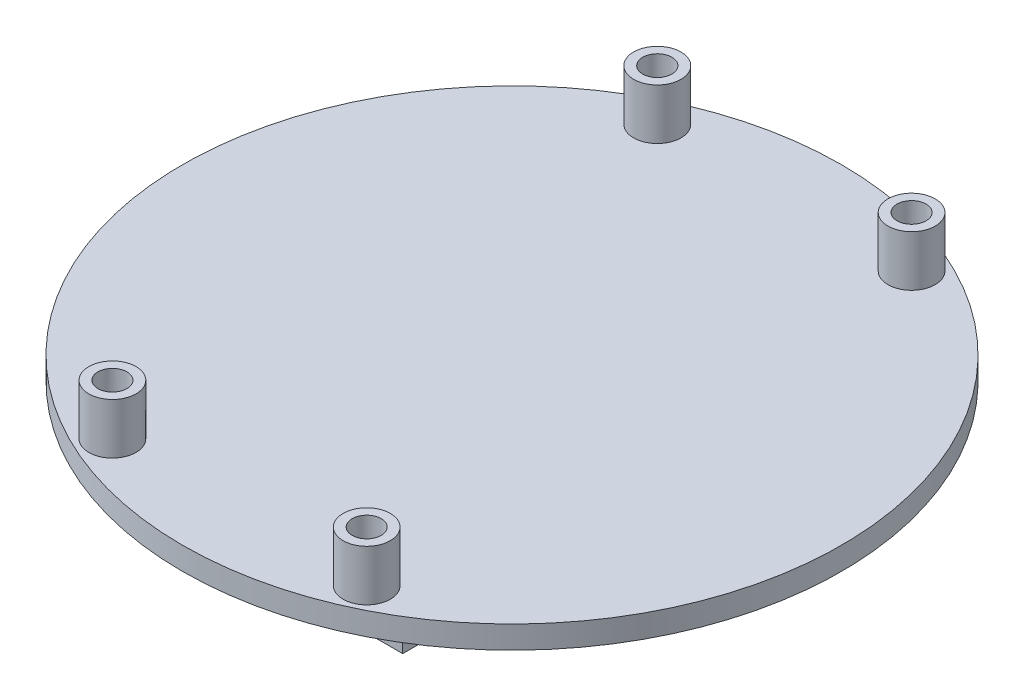
SolidWorks part; units mm, degrees
ref_plane "Alzado" through (0, 0, 0) normal (0, 0, 1) x (1, 0, 0)
ref_plane "Planta" through (0, 0, 0) normal (0, 1, 0) x (1, 0, 0)
ref_plane "Vista lateral" through (0, 0, 0) normal (1, 0, 0) x (0, 0, -1)
sketch "Croquis1" plane through (0, 0, 0) normal (0, 1, 0) x (1, 0, 0)
  circle A0 centre (0, 0) radius 36.29
  dimension "D1" = 72.58
extrude "Saliente-Extruir1" add sketch "Croquis1" along normal mid plane 2.5
sketch "Croquis2" plane through (0, -1.25, 0) normal (0, -1, 0) x (1, 0, 0)
  line L0 (-14.97, 27.005) -> (14.97, 27.005)
  line L1 (-13.97, -26.005) -> (13.97, -26.005)
  line L2 (-13.97, -26.005) -> (-13.97, 26.005)
  line L3 (-13.97, 26.005) -> (13.97, 26.005)
  line L4 (13.97, -26.005) -> (13.97, 26.005)
  line L5 (-13.97, -26.005) -> (13.97, 26.005) construction
  line L6 (-13.97, 26.005) -> (13.97, -26.005) construction
  line L7 (14.97, -27.005) -> (14.97, 27.005)
  line L8 (-14.97, -27.005) -> (14.97, -27.005)
  line L9 (-14.97, -27.005) -> (-14.97, 27.005)
  point P0 (-4.1318, -0.8767)
  dimension "D1" = 27.94
  dimension "D2" = 52.01
  dimension "D3" = 1
extrude "Saliente-Extruir2" add sketch "Croquis2" along normal blind 5
sketch "Croquis3" plane through (0, 1.25, 0) normal (0, 1, 0) x (1, 0, 0)
  circle A1 centre (14, 30) radius 1.6
  circle A2 centre (14, -30) radius 1.6
  circle A3 centre (-14, -30) radius 1.6
  circle A4 centre (-14, 30) radius 1.6073
  circle A5 centre (-14, 30) radius 2.6073
  circle A6 centre (14, 30) radius 2.6
  circle A7 centre (-14, -30) radius 2.6
  circle A8 centre (14, -30) radius 2.6
  dimension "D1" = 1
extrude "Saliente-Extruir3" add sketch "Croquis3" along normal blind 5.59
extrude "Cortar-Extruir1" cut sketch "Croquis3<3>" against normal through all contours A4 | A1 | A3 | A2 region at (14, 1.25, -30) region at (14, 1.25, 30) region at (-14, 1.25, 30) region at (-14, 1.25, -30)
sketch "Croquis3<3>" plane through (0, 1.25, 0) normal (0, 1, 0) x (1, 0, 0) same geometry as "Croquis3"
sketch "Croquis4" plane through (0, -1.25, 0) normal (0, -1, 0) x (1, 0, 0)
  line L0 (0, 0) -> (0, 30)
  line L1 (14, 30) -> (-14, 30)
